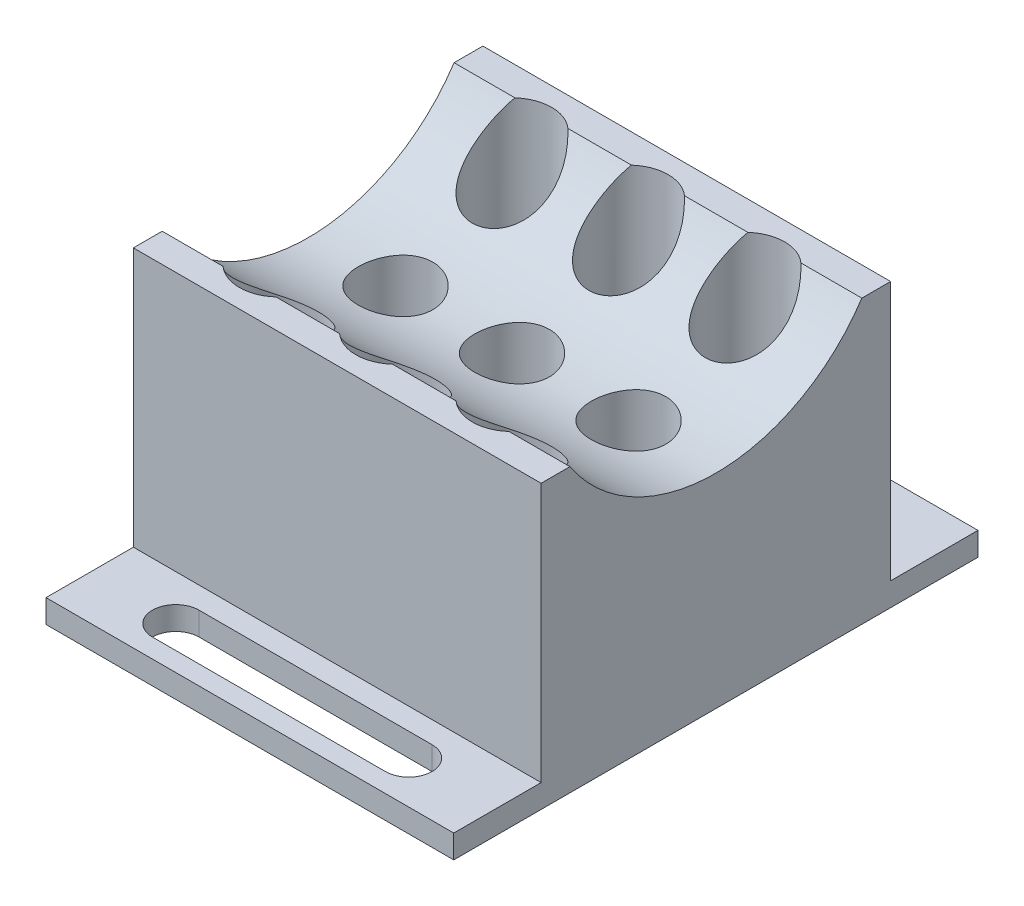
SolidWorks part; units mm, degrees
ref_plane "Front Plane" through (0, 0, 0) normal (0, 0, 1) x (1, 0, 0)
ref_plane "Top Plane" through (0, 0, 0) normal (0, 1, 0) x (1, 0, 0)
ref_plane "Right Plane" through (0, 0, 0) normal (1, 0, 0) x (0, 0, -1)
sketch "Sketch8" plane through (0, 0, 0) normal (0, 1, 0) x (1, 0, 0)
  line L1 (-17.5, -15) -> (17.5, -15)
  line L2 (-17.5, -15) -> (-17.5, 15)
  line L3 (-17.5, 15) -> (17.5, 15)
  line L4 (17.5, -15) -> (17.5, 15)
  line L5 (-17.5, -15) -> (17.5, 15) construction
  line L6 (-17.5, 15) -> (17.5, -15) construction
  point P0 (0, 0)
extrude "Boss-Extrude7" add sketch "Sketch8" along normal blind 80
sketch "Sketch10" plane through (0, 0, 0) normal (1, 0, 0) x (0, 0, -1)
  line L0 (0, 0) -> (0, 40) construction
  circle A0 centre (0, 40) radius 15
extrude "Cut-Extrude3" cut sketch "Sketch10" against normal through all and the other way through all
sketch "Sketch11" plane through (0, 0, 0) normal (1, 0, 0) x (0, 0, -1)
  line L1 (19.1682, 48.25) -> (-19.1682, 48.25)
  line L2 (19.1682, 48.25) -> (19.1682, 31.75)
  line L3 (19.1682, 31.75) -> (-19.1682, 31.75)
  line L4 (-19.1682, 48.25) -> (-19.1682, 31.75)
  line L5 (19.1682, 48.25) -> (-19.1682, 31.75) construction
  line L6 (19.1682, 31.75) -> (-19.1682, 48.25) construction
  point P0 (0, 40)
extrude "Cut-Extrude4" cut sketch "Sketch11" against normal through all both and the other way through all
sketch "Sketch12" plane through (0, 0, 0) normal (1, 0, 0) x (0, 0, -1)
  line L1 (17.3515, 0) -> (-16.4734, 0)
  line L2 (17.3515, 0) -> (17.3515, 7.5)
  line L3 (17.3515, 7.5) -> (-16.4734, 7.5)
  line L4 (-16.4734, 0) -> (-16.4734, 7.5)
extrude "Cut-Extrude5" cut sketch "Sketch12" against normal through all both and the other way through all
sketch "Sketch13" plane through (0, 0, 0) normal (1, 0, 0) x (0, 0, -1)
  line L1 (-29.3401, 40.0643) -> (16.2017, 40.0643)
  line L2 (-29.3401, 40.0643) -> (-29.3401, 81.5521)
  line L3 (-29.3401, 81.5521) -> (16.2017, 81.5521)
  line L4 (16.2017, 40.0643) -> (16.2017, 81.5521)
extrude "Cut-Extrude6" cut sketch "Sketch13" against normal through all both and the other way through all
ref_plane "Plane3" through (0, 7.5, 0) normal (0, -1, 0) x (-1, 0, 0)
sketch "Sketch15" plane through (0, 7.5, 0) normal (0, -1, 0) x (-1, 0, 0)
  line L1 (17.5, -15) -> (-17.5, -15)
  line L2 (17.5, -15) -> (17.5, -22.5)
  line L3 (17.5, -22.5) -> (-17.5, -22.5)
  line L4 (-17.5, -15) -> (-17.5, -22.5)
  line L5 (17.5, 15) -> (-17.5, 15)
  line L6 (17.5, 15) -> (17.5, 22.5)
  line L7 (17.5, 22.5) -> (-17.5, 22.5)
  line L8 (-17.5, 15) -> (-17.5, 22.5)
extrude "Boss-Extrude9" add sketch "Sketch15" against normal blind 2
sketch "Sketch16" plane through (0, 7.5, 0) normal (0, -1, 0) x (-1, 0, 0)
  line L0 (17.5, -22.5) -> (-17.5, -15.227) construction
  line L1 (-17.5, 22.5) -> (-17.5, -22.5) construction
  line L2 (-17.5, -22.5) -> (17.5, -15.227) construction
  line L3 (17.5, 22.5) -> (17.5, -22.5) construction
  line L4 (10, -18.8635) -> (-10, -18.8635) construction
  line L5 (10, -20.8635) -> (-10, -20.8635)
  line L6 (10, -16.8635) -> (-10, -16.8635)
  line L7 (17.5, 22.5) -> (-17.5, 15.1069) construction
  line L8 (-17.5, 22.5) -> (17.5, 15.1069) construction
  line L9 (10, 18.8035) -> (-10, 18.8035) construction
  line L10 (10, 16.8035) -> (-10, 16.8035)
  line L11 (10, 20.8035) -> (-10, 20.8035)
  arc A0 (10, -20.8635) -> (10, -16.8635) centre (10, -18.8635) ccw
  arc A1 (-10, -16.8635) -> (-10, -20.8635) centre (-10, -18.8635) ccw
  arc A2 (10, 16.8035) -> (10, 20.8035) centre (10, 18.8035) ccw
  arc A3 (-10, 20.8035) -> (-10, 16.8035) centre (-10, 18.8035) ccw
  point P12 (0, -18.8635)
  point P25 (0, 18.8035)
extrude "Cut-Extrude7" cut sketch "Sketch16" against normal blind 2
ref_plane "Plane5" through (0, 25, 0) normal (0, 1, 0) x (1, 0, 0)
sketch "Sketch18" plane through (0, 25, 0) normal (0, 1, 0) x (1, 0, 0)
  circle A0 centre (0, 0) radius 3.2
  circle A1 centre (10, 0) radius 3.2
  circle A2 centre (-10, 0) radius 3.2
  dimension "D1" = 2
  dimension "D2" = 2
extrude "Cut-Extrude10" cut sketch "Sketch18" against normal blind 6.4 and the other way through all
sketch "Sketch19" plane through (0, 25, 0) normal (0, 1, 0) x (1, 0, 0)
  line L0 (-10, 0) -> (-10, -10) construction
  circle A0 centre (-10, -10) radius 3.4
  circle A1 centre (0, -10) radius 3.4
  circle A2 centre (10, -10) radius 3.4
  circle A3 centre (-10, 10) radius 3.4
  circle A4 centre (0, 10) radius 3.4
  circle A5 centre (10, 10) radius 3.4
  dimension "D1" = 3
  dimension "D2" = 2
ref_plane "Plane6" through (-10, 0, 0) normal (-1, 0, 0) x (0, 0, 1)
sketch "Sketch20" plane through (-10, 0, 0) normal (-1, 0, 0) x (0, 0, 1)
  line L0 (10, 25) -> (6.6, 25) construction
  line L1 (0, 25) -> (10, 25) construction
  line L2 (6.6, 25) -> (6.6, 27.5032) construction
extrude "Cut-Extrude11" cut sketch "Sketch19" along normal up to next and the other way blind 4.9
